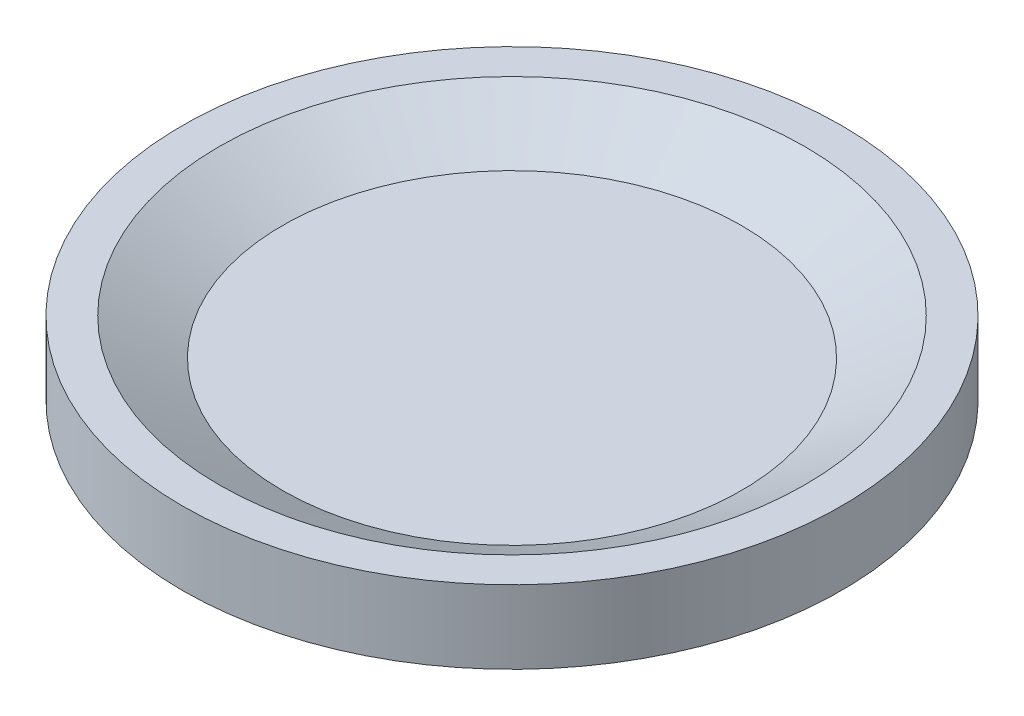
SolidWorks part; units mm, degrees
material "PLA/ABS"
ref_plane "Front Plane" through (0, 0, 0) normal (0, 0, 1) x (1, 0, 0)
ref_plane "Top Plane" through (0, 0, 0) normal (0, 1, 0) x (1, 0, 0)
ref_plane "Right Plane" through (0, 0, 0) normal (1, 0, 0) x (0, 0, -1)
other "Bounding Box"
ref_plane "Default Plane" through (-8.9266, -12.7485, 0) normal (-0.1736, 0.9848, 0) x (0.9848, 0.1736, 0)
sketch "Sketch2" plane through (0, 0, 0) normal (1, 0, 0) x (0, 0, -1)
  line L0 (0, 0) -> (0, 31713.5775) construction
  line L1 (0, 0) -> (31713.5775, 0) construction
  line L2 (0, 0) -> (0, -1.5875)
  line L3 (0, -1.5875) -> (-14.2875, -1.5875)
  line L4 (-14.2875, -1.5875) -> (-14.2875, 0)
  line L5 (-14.2875, 0) -> (-14.2875, 1.5875)
  line L6 (-14.2875, 1.5875) -> (-12.7, 1.5875)
  line L7 (-12.7, 1.5875) -> (-9.9504, 0)
  line L8 (-9.9504, 0) -> (0, 0)
  dimension "D1" = 28.575
  dimension "D2" = 3.175
  dimension "D3" = 1.5875
  dimension "D4" = 1.5875
  dimension "D5" = 30
revolve "Revolve1" add sketch "Sketch2" angle 360 about L0
